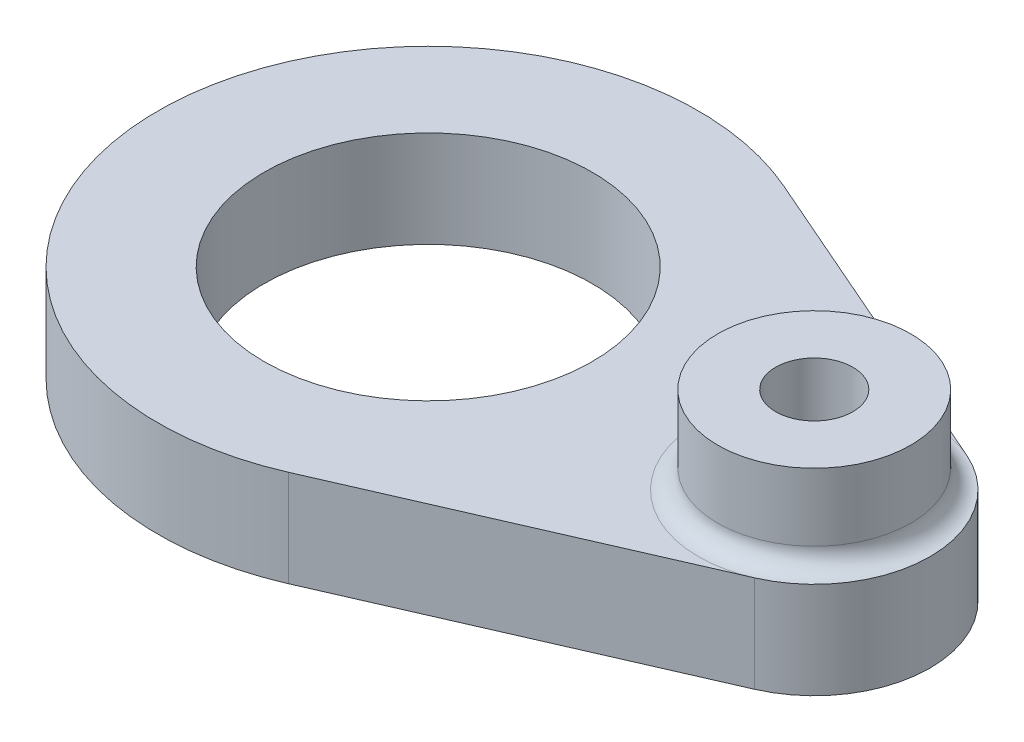
SolidWorks part; units mm, degrees
ref_plane "前视基准面" through (0, 0, 0) normal (0, 0, 1) x (1, 0, 0)
ref_plane "上视基准面" through (0, 0, 0) normal (0, 1, 0) x (1, 0, 0)
ref_plane "右视基准面" through (0, 0, 0) normal (1, 0, 0) x (0, 0, -1)
other "Configuration Table"
sketch "草图1" plane through (0, 0, 0) normal (0, 1, 0) x (1, 0, 0)
  line L1 (2.8, 6.4156) -> (11.2, 2.7495)
  line L2 (2.8, -6.4156) -> (11.2, -2.7495)
  circle A0 centre (0, 0) radius 4.25
  circle A1 centre (10, 0) radius 1
  circle A2 centre (0, 0) radius 7
  arc A3 (11.2, -2.7495) -> (11.2, 2.7495) centre (10, 0) ccw
extrude "凸台-拉伸1" add sketch "草图1" along normal blind 2.5 contours A2 A0 | L2 A3 L1 A2 A1 region at (8.8644, 0, 0) region at (5.691, 0, -3.7256)
sketch "草图2" plane through (0, 2.5, 0) normal (0, 1, 0) x (1, 0, 0)
  circle A0 centre (10, 0) radius 1
  circle A1 centre (10, 0) radius 2.5
extrude "凸台-拉伸2" add sketch "草图2" along normal blind 2.25
fillet "圆角2" radius 0.5 1 edges at (10, 2.5, 2.5)
